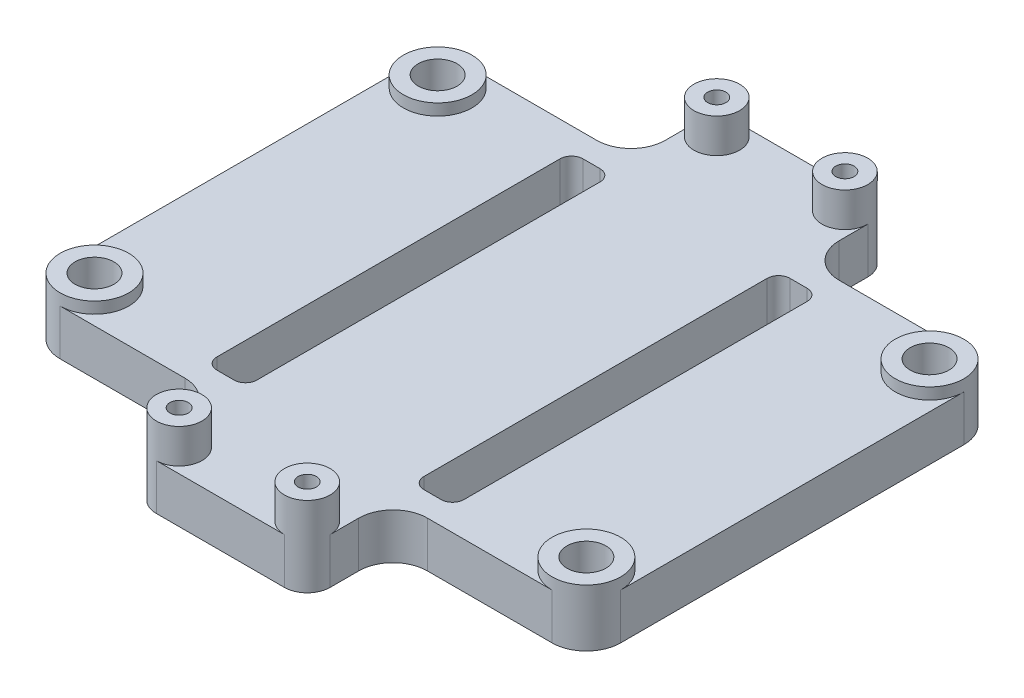
SolidWorks part; units mm, degrees
ref_plane "Front Plane" through (0, 0, 0) normal (0, 0, 1) x (1, 0, 0)
ref_plane "Top Plane" through (0, 0, 0) normal (0, 1, 0) x (1, 0, 0)
ref_plane "Right Plane" through (0, 0, 0) normal (1, 0, 0) x (0, 0, -1)
sketch "Sketch1" plane through (0, 0, 0) normal (0, 1, 0) x (1, 0, 0)
  line L1 (-21.5, -15) -> (21.5, -15) construction
  line L2 (-21.5, -15) -> (-21.5, 15) construction
  line L3 (-21.5, 15) -> (21.5, 15) construction
  line L4 (21.5, -15) -> (21.5, 15) construction
  line L5 (-21.5, -15) -> (21.5, 15) construction
  line L6 (-21.5, 15) -> (21.5, -15) construction
  circle A0 centre (-21.5, 15) radius 1.7
  circle A1 centre (-21.5, -15) radius 1.7
  circle A2 centre (21.5, -15) radius 1.7
  circle A3 centre (21.5, 15) radius 1.7
  circle A4 centre (-21.5, 15) radius 3
  circle A5 centre (-21.5, -15) radius 3
  circle A6 centre (21.5, -15) radius 3
  circle A7 centre (21.5, 15) radius 3
  point P0 (0, 0)
  dimension "D3" = 3.4
  dimension "D4" = 6
  dimension "D1" = 43
  dimension "D2" = 30
extrude "Boss-Extrude1" add sketch "Sketch1" along normal blind 5
sketch "Sketch2" plane through (0, 0, 0) normal (0, 1, 0) x (1, 0, 0)
  line L1 (-21.5, -18) -> (21.5, -18)
  line L2 (-24.5, -15) -> (-24.5, 15)
  line L3 (-21.5, 18) -> (21.5, 18)
  line L4 (24.5, -15) -> (24.5, 15)
  line L5 (-23.482, -17.2521) -> (23.482, 17.2521) construction
  line L6 (-23.482, 17.2521) -> (23.482, -17.2521) construction
  circle A0 centre (21.5, 15) radius 3 construction
  arc A1 (24.5, 15) -> (21.5, 18) centre (21.5, 15) ccw
  circle A2 centre (-21.5, 15) radius 3 construction
  arc A3 (-21.5, 18) -> (-24.5, 15) centre (-21.5, 15) ccw
  circle A4 centre (21.5, -15) radius 3 construction
  circle A5 centre (-21.5, -15) radius 3 construction
  arc A6 (21.5, -18) -> (24.5, -15) centre (21.5, -15) ccw
  arc A7 (-24.5, -15) -> (-21.5, -18) centre (-21.5, -15) ccw
  point P0 (0, 0)
  point P3 (-23.0507, 12.4319)
  point P11 (-18.54, -15.488)
extrude "Boss-Extrude2" add sketch "Sketch2" along normal blind 4
extrude "Cut-Extrude1" cut sketch "Sketch1<2>" against normal through all both and the other way through all contours A1 | A0 | A3 | A2 region at (-21.5, 0, -15) region at (-21.5, 0, 15) region at (21.5, 0, 15) region at (21.5, 0, -15)
sketch "Sketch1<2>" plane through (0, 0, 0) normal (0, 1, 0) x (1, 0, 0) same geometry as "Sketch1"
sketch "Sketch3" plane through (0, 0, 0) normal (0, 1, 0) x (1, 0, 0)
  line L1 (-5.6, -23.5) -> (5.6, -23.5) construction
  line L2 (-5.6, -23.5) -> (-5.6, 23.5) construction
  line L3 (-5.6, 23.5) -> (5.6, 23.5) construction
  line L4 (5.6, -23.5) -> (5.6, 23.5) construction
  line L5 (-5.6, -23.5) -> (5.6, 23.5) construction
  line L6 (-5.6, 23.5) -> (5.6, -23.5) construction
  circle A0 centre (-5.6, 23.5) radius 0.8
  circle A1 centre (5.6, 23.5) radius 0.8
  circle A2 centre (5.6, -23.5) radius 0.8
  circle A3 centre (-5.6, -23.5) radius 0.8
  circle A4 centre (-5.6, 23.5) radius 2
  circle A5 centre (5.6, 23.5) radius 2
  circle A6 centre (-5.6, -23.5) radius 2
  circle A7 centre (5.6, -23.5) radius 2
  point P0 (0, 0)
  dimension "D1" = 1.6
  dimension "D2" = 4
  dimension "D3" = 11.2
  dimension "D4" = 47
extrude "Boss-Extrude3" add sketch "Sketch3" along normal blind 7 separate body
sketch "Sketch4" plane through (0, 4, 0) normal (0, 1, 0) x (1, 0, 0)
  line L1 (-5.6, -25.5) -> (5.6, -25.5)
  line L2 (-7.6, -23.5) -> (-7.6, 23.5)
  line L3 (-5.6, 25.5) -> (5.6, 25.5)
  line L4 (7.6, -23.5) -> (7.6, 23.5)
  line L5 (-7.3121, -24.5339) -> (7.3121, 24.5339) construction
  line L6 (-7.3121, 24.5339) -> (7.3121, -24.5339) construction
  circle A0 centre (5.6, 23.5) radius 2 construction
  circle A1 centre (-5.6, 23.5) radius 2 construction
  circle A3 centre (5.6, -23.5) radius 2 construction
  circle A4 centre (-5.6, -23.5) radius 2 construction
  arc A5 (5.6, -25.5) -> (7.6, -23.5) centre (5.6, -23.5) ccw
  arc A6 (-7.6, -23.5) -> (-5.6, -25.5) centre (-5.6, -23.5) ccw
  arc A7 (7.6, 23.5) -> (5.6, 25.5) centre (5.6, 23.5) ccw
  arc A8 (-5.6, 25.5) -> (-7.6, 23.5) centre (-5.6, 23.5) ccw
  point P0 (0, 0)
  point P1 (-6.1107, 21.5663)
  point P16 (-4.1104, -24.8346)
extrude "Boss-Extrude4" add sketch "Sketch4" against normal up to surface (4 mm away) up to face at (21.5, 0, 16.7)
sketch "Sketch5" plane through (0, 0, 0) normal (0, -1, 0) x (1, 0, 0)
  line L1 (-10.5, -25.8) -> (10.5, -25.8) construction
  line L2 (-10.5, -25.8) -> (-10.5, 25.8) construction
  line L3 (-10.5, 25.8) -> (10.5, 25.8) construction
  line L4 (10.5, -25.8) -> (10.5, 25.8) construction
  line L5 (-10.5, -25.8) -> (10.5, 25.8) construction
  line L6 (-10.5, 25.8) -> (10.5, -25.8) construction
  point P0 (0, 0)
  dimension "D1" = 21
  dimension "D2" = 51.6
sketch "Sketch6" plane through (0, 4, 0) normal (0, 1, 0) x (1, 0, 0)
  line L0 (-7.6, 18) -> (-21.5, 18) construction
  line L1 (-7.3, -16) -> (-10.8, -16)
  line L2 (-7.3, -16) -> (-7.3, 16)
  line L3 (-7.3, 16) -> (-10.8, 16)
  line L4 (-10.8, -16) -> (-10.8, 16)
  line L5 (-7.3, -16) -> (-10.8, 16) construction
  line L6 (-7.3, 16) -> (-10.8, -16) construction
  line L7 (7.3, -16) -> (10.8, -16)
  line L8 (7.3, -16) -> (7.3, 16)
  line L9 (7.3, 16) -> (10.8, 16)
  line L10 (10.8, -16) -> (10.8, 16)
  line L11 (7.3, -16) -> (10.8, 16) construction
  line L12 (7.3, 16) -> (10.8, -16) construction
  point P0 (-9.05, 0)
  point P5 (9.05, 0)
  point P10 (0, 0)
  point P12 (-11.456, -3.7255)
  dimension "D1" = 7.3
  dimension "D2" = 7.3
  dimension "D3" = 3.5
  dimension "D4" = 2
extrude "Cut-Extrude2" cut sketch "Sketch6" against normal through all both and the other way through all
fillet "Fillet1" radius 1 8 edges at (7.3, 2, 16) (10.8, 2, 16) (-7.3, 2, 16) (-10.8, 2, 16) (7.3, 2, -16) (10.8, 2, -16) (-7.3, 2, -16) (-10.8, 2, -16)
fillet "Fillet2" radius 3 4 edges at (7.6, 2, 18) (-7.6, 2, 18) (-7.6, 2, -18) (7.6, 2, -18)
